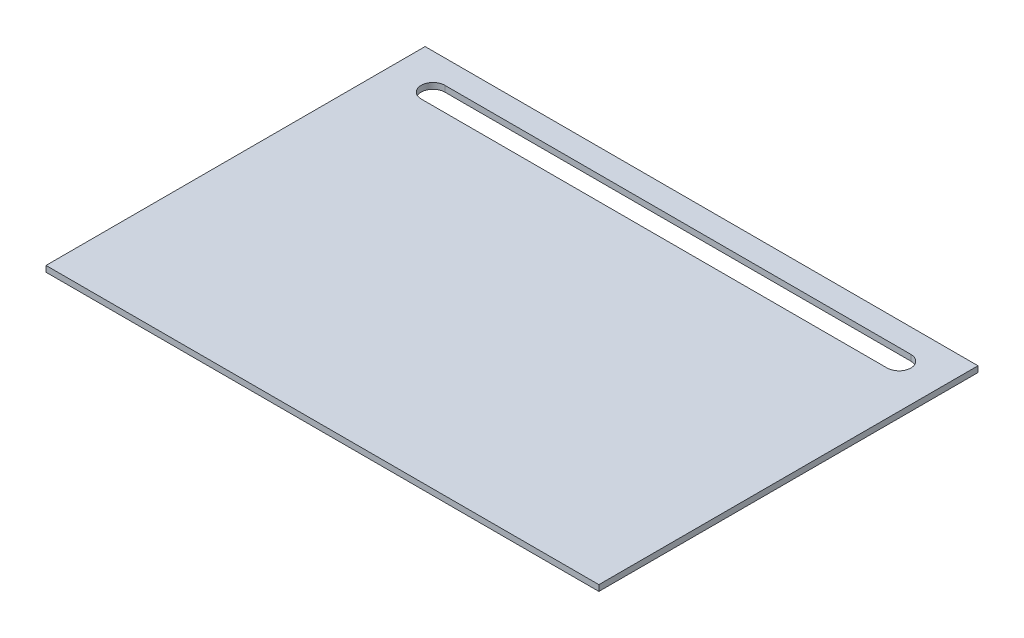
SolidWorks part; units mm, degrees
material "Maple"
ref_plane "Front Plane" through (0, 0, 0) normal (0, 0, 1) x (1, 0, 0)
ref_plane "Top Plane" through (0, 0, 0) normal (0, 1, 0) x (1, 0, 0)
ref_plane "Right Plane" through (0, 0, 0) normal (1, 0, 0) x (0, 0, -1)
sketch "Sketch1" plane through (0, 0, 0) normal (0, 1, 0) x (1, 0, 0)
  line L1 (-279.4, -152.4) -> (279.4, -152.4)
  line L2 (-279.4, -152.4) -> (-279.4, 152.4)
  line L3 (-279.4, 152.4) -> (279.4, 152.4)
  line L4 (279.4, -152.4) -> (279.4, 152.4)
  line L5 (-279.4, -152.4) -> (279.4, 152.4) construction
  line L6 (-279.4, 152.4) -> (279.4, -152.4) construction
  point P0 (0, 0)
  dimension "D1" = 304.8
  dimension "D2" = 558.8
extrude "Boss-Extrude1" add sketch "Sketch1" along normal mid plane 4.7625 contours L3 L4 L1 L2
sketch "Sketch2" plane through (0, 2.3813, 0) normal (0, 1, 0) x (1, 0, 0)
  line L0 (-279.4, -152.4) -> (-279.4, 152.4) construction
  line L1 (-279.4, 133.35) -> (-241.3, 133.35)
  line L2 (-279.4, 133.35) -> (-279.4, -133.35)
  line L3 (-279.4, -133.35) -> (-241.3, -133.35)
  line L4 (-241.3, 133.35) -> (-241.3, -133.35)
  line L5 (279.4, -152.4) -> (279.4, 152.4) construction
  line L6 (279.4, 133.35) -> (241.3, 133.35)
  line L7 (279.4, 133.35) -> (279.4, -133.35)
  line L8 (279.4, -133.35) -> (241.3, -133.35)
  line L9 (241.3, 133.35) -> (241.3, -133.35)
  line L10 (-241.3, 0) -> (241.3, 0) construction
  line L11 (-279.4, -152.4) -> (279.4, -152.4) construction
  dimension "D1" = 38.1
  dimension "D2" = 19.05
extrude "Cut-Extrude1" cut sketch "Sketch2" against normal through all
sketch "Sketch3" plane through (0, 2.3813, 0) normal (0, 1, 0) x (1, 0, 0)
  line L0 (-279.4, 152.4) -> (279.4, 152.4) construction
  line L1 (-190.5, 152.4) -> (190.5, 152.4)
  line L2 (-190.5, 152.4) -> (-190.5, 127)
  line L3 (-190.5, 127) -> (190.5, 127)
  line L4 (190.5, 152.4) -> (190.5, 127)
  line L5 (0, 0) -> (0, 127) construction
  line L6 (-241.3, -133.35) -> (-241.3, 133.35) construction
  dimension "D1" = 50.8
  dimension "D2" = 25.4
extrude "Cut-Extrude2" [suppressed] cut sketch "Sketch3" against normal through all
sketch "Sketch4" plane through (0, 2.3813, 0) normal (0, 1, 0) x (1, 0, 0)
  line L0 (-187.325, 123.825) -> (187.325, 123.825) construction
  line L1 (-187.325, 133.35) -> (187.325, 133.35)
  line L2 (-187.325, 114.3) -> (187.325, 114.3)
  line L3 (-279.4, -152.4) -> (279.4, -152.4) construction
  line L4 (-279.4, 152.4) -> (-222.25, 152.4)
  line L5 (-279.4, 152.4) -> (-279.4, -152.4)
  line L7 (0, 123.825) -> (0, 0) construction
  line L8 (-279.4, 152.4) -> (279.4, 152.4) construction
  line L9 (-279.4, -152.4) -> (-222.25, -152.4)
  line L10 (-222.25, 152.4) -> (-222.25, -152.4)
  line L12 (279.4, 152.4) -> (222.25, 152.4)
  line L13 (279.4, 152.4) -> (279.4, -152.4)
  line L14 (279.4, -152.4) -> (222.25, -152.4)
  line L15 (222.25, 152.4) -> (222.25, -152.4)
  arc A0 (-187.325, 133.35) -> (-187.325, 114.3) centre (-187.325, 123.825) ccw
  arc A1 (187.325, 114.3) -> (187.325, 133.35) centre (187.325, 123.825) ccw
  point P2 (0, 123.825)
  dimension "D1" = 25.4
  dimension "D2" = 19.05
  dimension "D3" = 19.05
  dimension "D4" = 57.15
extrude "Cut-Extrude3" cut sketch "Sketch4" against normal through all
sketch "Sketch5" [suppressed] plane through (0, 2.3813, 0) normal (0, 1, 0) x (1, 0, 0)
  line L0 (-222.25, 139.7) -> (-222.25, -139.7)
  line L1 (-279.4, 139.7) -> (279.4, 139.7) construction
  line L2 (-279.4, -139.7) -> (279.4, -139.7) construction
  line L3 (-279.4, -139.7) -> (-279.4, -120.65) construction
  dimension "D1" = 57.15
extrude "Cut-Extrude4" [suppressed] cut sketch "Sketch5" against normal through all and the other way through all
sketch "Sketch6" [suppressed] plane through (0, 2.3813, 0) normal (0, 1, 0) x (1, 0, 0)
  line L0 (-200.025, 111.125) -> (200.025, 111.125) construction
  line L1 (-200.025, 120.65) -> (200.025, 120.65)
  line L2 (-200.025, 101.6) -> (200.025, 101.6)
  line L3 (-298.45, 139.7) -> (298.45, 139.7) construction
  line L4 (298.45, -139.7) -> (298.45, 139.7) construction
  arc A0 (-200.025, 120.65) -> (-200.025, 101.6) centre (-200.025, 111.125) ccw
  arc A1 (200.025, 101.6) -> (200.025, 120.65) centre (200.025, 111.125) ccw
  point P2 (0, 111.125)
  dimension "D1" = 19.05
  dimension "D2" = 19.05
  dimension "D3" = 88.9
extrude "Cut-Extrude5" [suppressed] cut sketch "Sketch6" against normal through all
sketch "Sketch7" [suppressed] plane through (0, 2.3813, 0) normal (0, 1, 0) x (1, 0, 0)
  line L1 (-209.55, -44.45) -> (209.55, -44.45)
  line L2 (-209.55, -44.45) -> (-209.55, 44.45)
  line L3 (-209.55, 44.45) -> (209.55, 44.45)
  line L4 (209.55, -44.45) -> (209.55, 44.45)
  line L5 (-209.55, -44.45) -> (209.55, 44.45) construction
  line L6 (-209.55, 44.45) -> (209.55, -44.45) construction
  point P0 (0, 0)
  dimension "D1" = 88.9
  dimension "D2" = 444.5
extrude "Cut-Extrude6" [suppressed] cut sketch "Sketch7" against normal through all
